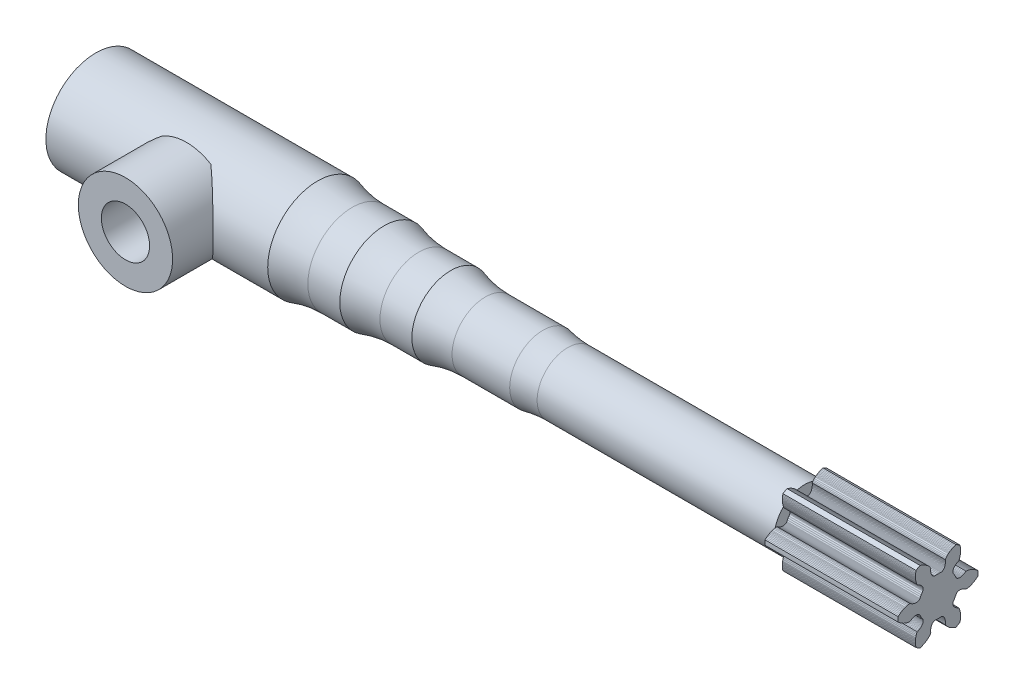
SolidWorks part; units mm, degrees
note: The reader was unsure of these and kept them because the rebuilt part matched: shared geometry of "Sketch5<2>".
ref_plane "Front Plane" through (0, 0, 0) normal (1, 0, 0) x (0, 1, 0)
ref_plane "Top Plane" through (0, 0, 0) normal (0, 0, 1) x (0, 1, 0)
ref_plane "Right Plane" through (0, 0, 0) normal (0, 1, 0) x (-1, 0, 0)
sketch "Sketch1" plane through (0, 0, 0) normal (1, 0, 0) x (0, 1, 0)
  line L0 (-1.7029, 2.65) -> (1.7029, 2.65)
  line L1 (-1.6733, 2.55) -> (1.6733, 2.55) construction
  circle A0 centre (0, 0) radius 3.15 construction
  circle A1 centre (0, 0) radius 4.5
  circle A2 centre (0, 0) radius 3.05
  dimension "D1" = 0.1
  dimension "D2" = 6.1
  dimension "D4" = 9
  dimension "D5" = 0.2
extrude "Boss-Extrude1" add sketch "Sketch1" along normal blind 14
sketch "Sketch2" plane through (14, 0, 0) normal (1, 0, 0) x (0, 1, 0)
  circle A0 centre (0, 0) radius 4.5
  circle A1 centre (0, 0) radius 4.5 construction
extrude "Boss-Extrude2" add sketch "Sketch2" along normal blind 6
sketch "Sketch5" plane through (0, 0, 2.65) normal (0, 0, -1) x (1, 0, 0)
  line L0 (0, 0) -> (14, 0) construction
  line L4 (0, 1.51) -> (0, -1.51)
  line L5 (0, -1.51) -> (14, -1.51)
  line L6 (14, -1.51) -> (14, 1.51)
  line L7 (14, 1.51) -> (0, 1.51)
  line L8 (0, 1.51) -> (0, -1.51) construction
  line L9 (0, -1.51) -> (14, -1.51) construction
  line L10 (14, -1.51) -> (14, 1.51) construction
  line L11 (14, 1.51) -> (0, 1.51) construction
  circle A0 centre (10.825, 0) radius 2.175
  circle A1 centre (10.825, 0) radius 4.25
  dimension "D3" = 4.35
  dimension "D4" = 8.5
  dimension "D2" = 1
  dimension "D1" = 0
extrude "Boss-Extrude4" add sketch "Sketch5" against normal blind 5.5
extrude "Cut-Extrude2" cut sketch "Sketch5<2>" against normal through all contours A0
sketch "Sketch5<2>" plane through (0, 0, 2.65) normal (0, 0, -1) x (1, 0, 0) same geometry as "Sketch5"
sketch "Sketch3" plane through (20, 0, 0) normal (1, 0, 0) x (0, 1, 0)
  circle A70 centre (0, 0) radius 4.5 construction
  circle A71 centre (0, 0) radius 4.5
  circle A72 centre (0, 0) radius 4
  dimension "D1" = 0.5
extrude "Boss-Extrude5" add sketch "Sketch3" along normal blind 6 contours A72
sketch "Sketch6" plane through (26, 0, 0) normal (1, 0, 0) x (0, 1, 0)
  circle A0 centre (0, 0) radius 4 construction
  circle A1 centre (0, 0) radius 4
  circle A2 centre (0, 0) radius 3.5
  dimension "D1" = 0.5
extrude "Boss-Extrude6" add sketch "Sketch6" along normal blind 6 contours A2
sketch "Sketch7" plane through (32, 0, 0) normal (1, 0, 0) x (0, 1, 0)
  circle A0 centre (0, 0) radius 3.5 construction
  circle A1 centre (0, 0) radius 3.5
  circle A2 centre (0, 0) radius 3
  dimension "D1" = 0.5
extrude "Boss-Extrude7" add sketch "Sketch7" along normal blind 8.32 contours A2
sketch "Sketch8" plane through (40.32, 0, 0) normal (1, 0, 0) x (0, 1, 0)
  circle A0 centre (0, 0) radius 3 construction
  circle A1 centre (0, 0) radius 3
  circle A2 centre (0, 0) radius 2.75
  dimension "D1" = 0.25
extrude "Boss-Extrude8" add sketch "Sketch8" along normal blind 23.6 contours A2
sketch "Sketch10" plane through (63.92, 0, 0) normal (1, 0, 0) x (0, 1, 0)
  line L0 (-0.2676, -3.5489) -> (-0.3294, -3.471)
  line L1 (-0.3294, -3.471) -> (-0.3862, -3.3929)
  line L2 (-0.3862, -3.3929) -> (-0.437, -3.3167)
  line L3 (-0.437, -3.3167) -> (-0.483, -3.2409)
  line L4 (-0.483, -3.2409) -> (-0.5222, -3.1698)
  line L5 (-0.5222, -3.1698) -> (-0.5578, -3.0984)
  line L6 (-0.5578, -3.0984) -> (-0.5877, -3.0315)
  line L7 (-0.5877, -3.0315) -> (-0.6137, -2.9659)
  line L8 (-0.6137, -2.9659) -> (-0.6533, -2.8448)
  line L9 (-0.6533, -2.8448) -> (-0.6779, -2.7405)
  line L10 (-0.6779, -2.7405) -> (-0.6912, -2.651)
  line L11 (-0.6912, -2.651) -> (-0.6959, -2.5788)
  line L12 (-0.6959, -2.5788) -> (-0.6958, -2.5445)
  line L13 (-0.6958, -2.5445) -> (-0.6453, -2.4741)
  line L14 (-0.6453, -2.4741) -> (-0.6007, -2.4024)
  line L15 (-0.6007, -2.4024) -> (-0.5632, -2.3314)
  line L16 (-0.5632, -2.3314) -> (-0.5325, -2.2616)
  line L17 (-0.5325, -2.2616) -> (-0.5087, -2.1934)
  line L18 (-0.5087, -2.1934) -> (-0.4913, -2.1274)
  line L19 (-0.4913, -2.1274) -> (-0.4802, -2.0638)
  line L20 (-0.4802, -2.0638) -> (-0.4753, -2.0031)
  line L21 (-0.4753, -2.0031) -> (-0.4761, -1.9458)
  line L22 (-0.4761, -1.9458) -> (-0.4824, -1.8921)
  line L23 (-0.4824, -1.8921) -> (-0.4939, -1.8425)
  line L24 (-0.4939, -1.8425) -> (-0.5102, -1.7972)
  line L25 (-0.5102, -1.7972) -> (-0.5311, -1.7566)
  line L26 (-0.5311, -1.7566) -> (-0.5561, -1.721)
  line L27 (-0.5561, -1.721) -> (-0.5848, -1.6906)
  line L28 (-0.5848, -1.6906) -> (-0.6169, -1.6657)
  line L29 (-0.6169, -1.6657) -> (-0.6341, -1.6554)
  line L30 (-0.6341, -1.6554) -> (-0.7518, -1.6022)
  line L31 (-0.7518, -1.6022) -> (-0.8694, -1.5401)
  line L32 (-0.8694, -1.5401) -> (-0.9819, -1.4693)
  line L33 (-0.9819, -1.4693) -> (-1.0868, -1.394)
  line L34 (-1.0868, -1.394) -> (-1.1043, -1.3843)
  line L35 (-1.1043, -1.3843) -> (-1.142, -1.3689)
  line L36 (-1.142, -1.3689) -> (-1.1827, -1.3592)
  line L37 (-1.1827, -1.3592) -> (-1.226, -1.3554)
  line L38 (-1.226, -1.3554) -> (-1.2716, -1.3576)
  line L39 (-1.2716, -1.3576) -> (-1.319, -1.3661)
  line L40 (-1.319, -1.3661) -> (-1.3677, -1.381)
  line L41 (-1.3677, -1.381) -> (-1.4174, -1.4023)
  line L42 (-1.4174, -1.4023) -> (-1.4674, -1.4303)
  line L43 (-1.4674, -1.4303) -> (-1.5175, -1.465)
  line L44 (-1.5175, -1.465) -> (-1.567, -1.5063)
  line L45 (-1.567, -1.5063) -> (-1.6155, -1.5544)
  line L46 (-1.6155, -1.5544) -> (-1.6626, -1.6091)
  line L47 (-1.6626, -1.6091) -> (-1.7077, -1.6706)
  line L48 (-1.7077, -1.6706) -> (-1.7504, -1.7386)
  line L49 (-1.7504, -1.7386) -> (-1.7903, -1.813)
  line L50 (-1.7903, -1.813) -> (-1.826, -1.892)
  line L51 (-1.826, -1.892) -> (-1.8556, -1.9092)
  line L52 (-1.8556, -1.9092) -> (-1.9205, -1.9413)
  line L53 (-1.9205, -1.9413) -> (-2.0047, -1.9745)
  line L54 (-2.0047, -1.9745) -> (-2.1073, -2.0053)
  line L55 (-2.1073, -2.0053) -> (-2.2319, -2.0316)
  line L56 (-2.2319, -2.0316) -> (-2.3018, -2.0418)
  line L57 (-2.3018, -2.0418) -> (-2.3747, -2.0494)
  line L58 (-2.3747, -2.0494) -> (-2.4543, -2.0543)
  line L59 (-2.4543, -2.0543) -> (-2.5355, -2.0559)
  line L60 (-2.5355, -2.0559) -> (-2.6241, -2.054)
  line L61 (-2.6241, -2.054) -> (-2.7155, -2.0481)
  line L62 (-2.7155, -2.0481) -> (-2.8116, -2.0379)
  line L63 (-2.8116, -2.0379) -> (-2.9099, -2.0233)
  line L64 (-2.9099, -2.0233) -> (-3.0047, -2.0052)
  line L65 (-3.2164, -1.6385) -> (-3.1847, -1.5473)
  line L66 (-3.1847, -1.5473) -> (-3.1482, -1.4549)
  line L67 (-3.1482, -1.4549) -> (-3.109, -1.3666)
  line L68 (-3.109, -1.3666) -> (-3.0684, -1.2845)
  line L69 (-3.0684, -1.2845) -> (-3.0257, -1.2068)
  line L70 (-3.0257, -1.2068) -> (-2.9837, -1.1373)
  line L71 (-2.9837, -1.1373) -> (-2.9397, -1.0708)
  line L72 (-2.9397, -1.0708) -> (-2.8967, -1.0114)
  line L73 (-2.8967, -1.0114) -> (-2.8529, -0.9561)
  line L74 (-2.8529, -0.9561) -> (-2.7678, -0.8613)
  line L75 (-2.7678, -0.8613) -> (-2.6898, -0.7879)
  line L76 (-2.6898, -0.7879) -> (-2.619, -0.7315)
  line L77 (-2.619, -0.7315) -> (-2.5587, -0.6914)
  line L78 (-2.5587, -0.6914) -> (-2.529, -0.6743)
  line L79 (-2.529, -0.6743) -> (-2.4428, -0.6829)
  line L80 (-2.4428, -0.6829) -> (-2.3584, -0.6856)
  line L81 (-2.3584, -0.6856) -> (-2.2781, -0.6826)
  line L82 (-2.2781, -0.6826) -> (-2.2024, -0.6742)
  line L83 (-2.2024, -0.6742) -> (-2.1314, -0.6608)
  line L84 (-2.1314, -0.6608) -> (-2.0655, -0.6428)
  line L85 (-2.0655, -0.6428) -> (-2.0049, -0.6206)
  line L86 (-2.0049, -0.6206) -> (-1.9499, -0.5946)
  line L87 (-1.9499, -0.5946) -> (-1.9006, -0.5653)
  line L88 (-1.9006, -0.5653) -> (-1.8573, -0.533)
  line L89 (-1.8573, -0.533) -> (-1.8201, -0.4982)
  line L90 (-1.8201, -0.4982) -> (-1.789, -0.4614)
  line L91 (-1.789, -0.4614) -> (-1.7643, -0.423)
  line L92 (-1.7643, -0.423) -> (-1.746, -0.3836)
  line L93 (-1.746, -0.3836) -> (-1.734, -0.3435)
  line L94 (-1.734, -0.3435) -> (-1.7285, -0.3032)
  line L95 (-1.7285, -0.3032) -> (-1.7282, -0.2831)
  line L96 (-1.7282, -0.2831) -> (-1.7409, -0.1546)
  line L97 (-1.7409, -0.1546) -> (-1.746, -0.0218)
  line L98 (-1.746, -0.0218) -> (-1.7409, 0.111)
  line L99 (-1.7409, 0.111) -> (-1.7282, 0.2395)
  line L100 (-1.7282, 0.2395) -> (-1.7285, 0.2596)
  line L101 (-1.7285, 0.2596) -> (-1.734, 0.2999)
  line L102 (-1.734, 0.2999) -> (-1.746, 0.34)
  line L103 (-1.746, 0.34) -> (-1.7643, 0.3794)
  line L104 (-1.7643, 0.3794) -> (-1.789, 0.4178)
  line L105 (-1.789, 0.4178) -> (-1.8201, 0.4546)
  line L106 (-1.8201, 0.4546) -> (-1.8573, 0.4894)
  line L107 (-1.8573, 0.4894) -> (-1.9006, 0.5217)
  line L108 (-1.9006, 0.5217) -> (-1.9499, 0.551)
  line L109 (-1.9499, 0.551) -> (-2.0049, 0.577)
  line L110 (-2.0049, 0.577) -> (-2.0655, 0.5992)
  line L111 (-2.0655, 0.5992) -> (-2.1314, 0.6172)
  line L112 (-2.1314, 0.6172) -> (-2.2024, 0.6306)
  line L113 (-2.2024, 0.6306) -> (-2.2781, 0.639)
  line L114 (-2.2781, 0.639) -> (-2.3584, 0.642)
  line L115 (-2.3584, 0.642) -> (-2.4428, 0.6393)
  line L116 (-2.4428, 0.6393) -> (-2.529, 0.6307)
  line L117 (-2.529, 0.6307) -> (-2.5587, 0.6478)
  line L118 (-2.5587, 0.6478) -> (-2.619, 0.6879)
  line L119 (-2.619, 0.6879) -> (-2.6898, 0.7443)
  line L120 (-2.6898, 0.7443) -> (-2.7678, 0.8177)
  line L121 (-2.7678, 0.8177) -> (-2.8529, 0.9125)
  line L122 (-2.8529, 0.9125) -> (-2.8967, 0.9678)
  line L123 (-2.8967, 0.9678) -> (-2.9397, 1.0272)
  line L124 (-2.9397, 1.0272) -> (-2.9837, 1.0937)
  line L125 (-2.9837, 1.0937) -> (-3.0257, 1.1632)
  line L126 (-3.0257, 1.1632) -> (-3.0684, 1.2409)
  line L127 (-3.0684, 1.2409) -> (-3.109, 1.323)
  line L128 (-3.109, 1.323) -> (-3.1482, 1.4113)
  line L129 (-3.1482, 1.4113) -> (-3.1847, 1.5037)
  line L130 (-3.1847, 1.5037) -> (-3.2164, 1.5949)
  line L131 (-3.0047, 1.9616) -> (-2.9099, 1.9797)
  line L132 (-2.9099, 1.9797) -> (-2.8116, 1.9943)
  line L133 (-2.8116, 1.9943) -> (-2.7155, 2.0045)
  line L134 (-2.7155, 2.0045) -> (-2.6241, 2.0104)
  line L135 (-2.6241, 2.0104) -> (-2.5355, 2.0123)
  line L136 (-2.5355, 2.0123) -> (-2.4543, 2.0107)
  line L137 (-2.4543, 2.0107) -> (-2.3747, 2.0058)
  line L138 (-2.3747, 2.0058) -> (-2.3018, 1.9983)
  line L139 (-2.3018, 1.9983) -> (-2.2319, 1.988)
  line L140 (-2.2319, 1.988) -> (-2.1073, 1.9617)
  line L141 (-2.1073, 1.9617) -> (-2.0047, 1.9309)
  line L142 (-2.0047, 1.9309) -> (-1.9205, 1.8977)
  line L143 (-1.9205, 1.8977) -> (-1.8556, 1.8656)
  line L144 (-1.8556, 1.8656) -> (-1.826, 1.8484)
  line L145 (-1.826, 1.8484) -> (-1.7903, 1.7694)
  line L146 (-1.7903, 1.7694) -> (-1.7504, 1.695)
  line L147 (-1.7504, 1.695) -> (-1.7077, 1.627)
  line L148 (-1.7077, 1.627) -> (-1.6626, 1.5656)
  line L149 (-1.6626, 1.5656) -> (-1.6155, 1.5108)
  line L150 (-1.6155, 1.5108) -> (-1.567, 1.4627)
  line L151 (-1.567, 1.4627) -> (-1.5175, 1.4214)
  line L152 (-1.5175, 1.4214) -> (-1.4674, 1.3867)
  line L153 (-1.4674, 1.3867) -> (-1.4174, 1.3587)
  line L154 (-1.4174, 1.3587) -> (-1.3677, 1.3374)
  line L155 (-1.3677, 1.3374) -> (-1.319, 1.3225)
  line L156 (-1.319, 1.3225) -> (-1.2716, 1.314)
  line L157 (-1.2716, 1.314) -> (-1.226, 1.3118)
  line L158 (-1.226, 1.3118) -> (-1.1827, 1.3156)
  line L159 (-1.1827, 1.3156) -> (-1.142, 1.3254)
  line L160 (-1.142, 1.3254) -> (-1.1043, 1.3407)
  line L161 (-1.1043, 1.3407) -> (-1.0868, 1.3504)
  line L162 (-1.0868, 1.3504) -> (-0.9819, 1.4257)
  line L163 (-0.9819, 1.4257) -> (-0.8694, 1.4965)
  line L164 (-0.8694, 1.4965) -> (-0.7518, 1.5586)
  line L165 (-0.7518, 1.5586) -> (-0.6341, 1.6118)
  line L166 (-0.6341, 1.6118) -> (-0.6169, 1.6221)
  line L167 (-0.6169, 1.6221) -> (-0.5848, 1.647)
  line L168 (-0.5848, 1.647) -> (-0.5561, 1.6774)
  line L169 (-0.5561, 1.6774) -> (-0.5311, 1.713)
  line L170 (-0.5311, 1.713) -> (-0.5102, 1.7536)
  line L171 (-0.5102, 1.7536) -> (-0.4939, 1.7989)
  line L172 (-0.4939, 1.7989) -> (-0.4824, 1.8485)
  line L173 (-0.4824, 1.8485) -> (-0.4761, 1.9022)
  line L174 (-0.4761, 1.9022) -> (-0.4753, 1.9596)
  line L175 (-0.4753, 1.9596) -> (-0.4802, 2.0202)
  line L176 (-0.4802, 2.0202) -> (-0.4913, 2.0838)
  line L177 (-0.4913, 2.0838) -> (-0.5087, 2.1498)
  line L178 (-0.5087, 2.1498) -> (-0.5325, 2.218)
  line L179 (-0.5325, 2.218) -> (-0.5632, 2.2878)
  line L180 (-0.5632, 2.2878) -> (-0.6007, 2.3588)
  line L181 (-0.6007, 2.3588) -> (-0.6453, 2.4305)
  line L182 (-0.6453, 2.4305) -> (-0.6958, 2.5009)
  line L183 (-0.6958, 2.5009) -> (-0.6959, 2.5352)
  line L184 (-0.6959, 2.5352) -> (-0.6912, 2.6074)
  line L185 (-0.6912, 2.6074) -> (-0.6779, 2.6969)
  line L186 (-0.6779, 2.6969) -> (-0.6533, 2.8012)
  line L187 (-0.6533, 2.8012) -> (-0.6137, 2.9223)
  line L188 (-0.6137, 2.9223) -> (-0.5877, 2.9879)
  line L189 (-0.5877, 2.9879) -> (-0.5578, 3.0548)
  line L190 (-0.5578, 3.0548) -> (-0.5222, 3.1262)
  line L191 (-0.5222, 3.1262) -> (-0.483, 3.1973)
  line L192 (-0.483, 3.1973) -> (-0.437, 3.2731)
  line L193 (-0.437, 3.2731) -> (-0.3862, 3.3493)
  line L194 (-0.3862, 3.3493) -> (-0.3294, 3.4275)
  line L195 (-0.3294, 3.4275) -> (-0.2676, 3.5053)
  line L196 (-0.2676, 3.5053) -> (-0.2045, 3.5783)
  line L197 (0.2189, 3.5783) -> (0.282, 3.5053)
  line L198 (0.282, 3.5053) -> (0.3438, 3.4275)
  line L199 (0.3438, 3.4275) -> (0.4007, 3.3493)
  line L200 (0.4007, 3.3493) -> (0.4515, 3.2731)
  line L201 (0.4515, 3.2731) -> (0.4975, 3.1973)
  line L202 (0.4975, 3.1973) -> (0.5367, 3.1262)
  line L203 (0.5367, 3.1262) -> (0.5722, 3.0548)
  line L204 (0.5722, 3.0548) -> (0.6021, 2.9879)
  line L205 (0.6021, 2.9879) -> (0.6282, 2.9223)
  line L206 (0.6282, 2.9223) -> (0.6677, 2.8012)
  line L207 (0.6677, 2.8012) -> (0.6923, 2.6969)
  line L208 (0.6923, 2.6969) -> (0.7057, 2.6074)
  line L209 (0.7057, 2.6074) -> (0.7104, 2.5352)
  line L210 (0.7104, 2.5352) -> (0.7103, 2.5009)
  line L211 (0.7103, 2.5009) -> (0.6597, 2.4305)
  line L212 (0.6597, 2.4305) -> (0.6152, 2.3588)
  line L213 (0.6152, 2.3588) -> (0.5776, 2.2878)
  line L214 (0.5776, 2.2878) -> (0.547, 2.218)
  line L215 (0.547, 2.218) -> (0.5231, 2.1498)
  line L216 (0.5231, 2.1498) -> (0.5058, 2.0838)
  line L217 (0.5058, 2.0838) -> (0.4947, 2.0202)
  line L218 (0.4947, 2.0202) -> (0.4897, 1.9596)
  line L219 (0.4897, 1.9596) -> (0.4905, 1.9022)
  line L220 (0.4905, 1.9022) -> (0.4968, 1.8485)
  line L221 (0.4968, 1.8485) -> (0.5083, 1.7989)
  line L222 (0.5083, 1.7989) -> (0.5247, 1.7536)
  line L223 (0.5247, 1.7536) -> (0.5455, 1.713)
  line L224 (0.5455, 1.713) -> (0.5705, 1.6774)
  line L225 (0.5705, 1.6774) -> (0.5993, 1.647)
  line L226 (0.5993, 1.647) -> (0.6314, 1.6221)
  line L227 (0.6314, 1.6221) -> (0.6486, 1.6118)
  line L228 (0.6486, 1.6118) -> (0.7663, 1.5586)
  line L229 (0.7663, 1.5586) -> (0.8838, 1.4965)
  line L230 (0.8838, 1.4965) -> (0.9964, 1.4257)
  line L231 (0.9964, 1.4257) -> (1.1013, 1.3504)
  line L232 (1.1013, 1.3504) -> (1.1188, 1.3407)
  line L233 (1.1188, 1.3407) -> (1.1564, 1.3254)
  line L234 (1.1564, 1.3254) -> (1.1971, 1.3156)
  line L235 (1.1971, 1.3156) -> (1.2405, 1.3118)
  line L236 (1.2405, 1.3118) -> (1.2861, 1.314)
  line L237 (1.2861, 1.314) -> (1.3335, 1.3225)
  line L238 (1.3335, 1.3225) -> (1.3822, 1.3374)
  line L239 (1.3822, 1.3374) -> (1.4318, 1.3587)
  line L240 (1.4318, 1.3587) -> (1.4819, 1.3867)
  line L241 (1.4819, 1.3867) -> (1.5319, 1.4214)
  line L242 (1.5319, 1.4214) -> (1.5814, 1.4627)
  line L243 (1.5814, 1.4627) -> (1.63, 1.5108)
  line L244 (1.63, 1.5108) -> (1.6771, 1.5656)
  line L245 (1.6771, 1.5656) -> (1.7222, 1.627)
  line L246 (1.7222, 1.627) -> (1.7649, 1.695)
  line L247 (1.7649, 1.695) -> (1.8048, 1.7694)
  line L248 (1.8048, 1.7694) -> (1.8405, 1.8484)
  line L249 (1.8405, 1.8484) -> (1.8701, 1.8656)
  line L250 (1.8701, 1.8656) -> (1.935, 1.8977)
  line L251 (1.935, 1.8977) -> (2.0192, 1.9309)
  line L252 (2.0192, 1.9309) -> (2.1217, 1.9617)
  line L253 (2.1217, 1.9617) -> (2.2464, 1.988)
  line L254 (2.2464, 1.988) -> (2.3162, 1.9983)
  line L255 (2.3162, 1.9983) -> (2.3891, 2.0058)
  line L256 (2.3891, 2.0058) -> (2.4688, 2.0107)
  line L257 (2.4688, 2.0107) -> (2.55, 2.0123)
  line L258 (2.55, 2.0123) -> (2.6386, 2.0104)
  line L259 (2.6386, 2.0104) -> (2.73, 2.0045)
  line L260 (2.73, 2.0045) -> (2.8261, 1.9943)
  line L261 (2.8261, 1.9943) -> (2.9243, 1.9797)
  line L262 (2.9243, 1.9797) -> (3.0192, 1.9616)
  line L263 (3.2309, 1.5949) -> (3.1992, 1.5037)
  line L264 (3.1992, 1.5037) -> (3.1627, 1.4113)
  line L265 (3.1627, 1.4113) -> (3.1235, 1.323)
  line L266 (3.1235, 1.323) -> (3.0828, 1.2409)
  line L267 (3.0828, 1.2409) -> (3.0402, 1.1632)
  line L268 (3.0402, 1.1632) -> (2.9982, 1.0937)
  line L269 (2.9982, 1.0937) -> (2.9542, 1.0272)
  line L270 (2.9542, 1.0272) -> (2.9112, 0.9678)
  line L271 (2.9112, 0.9678) -> (2.8674, 0.9125)
  line L272 (2.8674, 0.9125) -> (2.7823, 0.8177)
  line L273 (2.7823, 0.8177) -> (2.7043, 0.7443)
  line L274 (2.7043, 0.7443) -> (2.6335, 0.6879)
  line L275 (2.6335, 0.6879) -> (2.5732, 0.6478)
  line L276 (2.5732, 0.6478) -> (2.5435, 0.6307)
  line L277 (2.5435, 0.6307) -> (2.4573, 0.6393)
  line L278 (2.4573, 0.6393) -> (2.3728, 0.642)
  line L279 (2.3728, 0.642) -> (2.2926, 0.639)
  line L280 (2.2926, 0.639) -> (2.2168, 0.6306)
  line L281 (2.2168, 0.6306) -> (2.1459, 0.6172)
  line L282 (2.1459, 0.6172) -> (2.08, 0.5992)
  line L283 (2.08, 0.5992) -> (2.0194, 0.577)
  line L284 (2.0194, 0.577) -> (1.9644, 0.551)
  line L285 (1.9644, 0.551) -> (1.9151, 0.5217)
  line L286 (1.9151, 0.5217) -> (1.8718, 0.4894)
  line L287 (1.8718, 0.4894) -> (1.8346, 0.4546)
  line L288 (1.8346, 0.4546) -> (1.8035, 0.4178)
  line L289 (1.8035, 0.4178) -> (1.7788, 0.3794)
  line L290 (1.7788, 0.3794) -> (1.7604, 0.34)
  line L291 (1.7604, 0.34) -> (1.7485, 0.2999)
  line L292 (1.7485, 0.2999) -> (1.743, 0.2596)
  line L293 (1.743, 0.2596) -> (1.7426, 0.2395)
  line L294 (1.7426, 0.2395) -> (1.7554, 0.111)
  line L295 (1.7554, 0.111) -> (1.7604, -0.0218)
  line L296 (1.7604, -0.0218) -> (1.7554, -0.1546)
  line L297 (1.7554, -0.1546) -> (1.7426, -0.2831)
  line L298 (1.7426, -0.2831) -> (1.743, -0.3032)
  line L299 (1.743, -0.3032) -> (1.7485, -0.3435)
  line L300 (1.7485, -0.3435) -> (1.7604, -0.3836)
  line L301 (1.7604, -0.3836) -> (1.7788, -0.423)
  line L302 (1.7788, -0.423) -> (1.8035, -0.4614)
  line L303 (1.8035, -0.4614) -> (1.8346, -0.4982)
  line L304 (1.8346, -0.4982) -> (1.8718, -0.533)
  line L305 (1.8718, -0.533) -> (1.9151, -0.5653)
  line L306 (1.9151, -0.5653) -> (1.9644, -0.5946)
  line L307 (1.9644, -0.5946) -> (2.0194, -0.6206)
  line L308 (2.0194, -0.6206) -> (2.08, -0.6428)
  line L309 (2.08, -0.6428) -> (2.1459, -0.6608)
  line L310 (2.1459, -0.6608) -> (2.2168, -0.6742)
  line L311 (2.2168, -0.6742) -> (2.2926, -0.6826)
  line L312 (2.2926, -0.6826) -> (2.3728, -0.6856)
  line L313 (2.3728, -0.6856) -> (2.4573, -0.6829)
  line L314 (2.4573, -0.6829) -> (2.5435, -0.6743)
  line L315 (2.5435, -0.6743) -> (2.5732, -0.6914)
  line L316 (2.5732, -0.6914) -> (2.6335, -0.7315)
  line L317 (2.6335, -0.7315) -> (2.7043, -0.7879)
  line L318 (2.7043, -0.7879) -> (2.7823, -0.8613)
  line L319 (2.7823, -0.8613) -> (2.8674, -0.9561)
  line L320 (2.8674, -0.9561) -> (2.9112, -1.0114)
  line L321 (2.9112, -1.0114) -> (2.9542, -1.0708)
  line L322 (2.9542, -1.0708) -> (2.9982, -1.1373)
  line L323 (2.9982, -1.1373) -> (3.0402, -1.2068)
  line L324 (3.0402, -1.2068) -> (3.0828, -1.2845)
  line L325 (3.0828, -1.2845) -> (3.1235, -1.3666)
  line L326 (3.1235, -1.3666) -> (3.1627, -1.4549)
  line L327 (3.1627, -1.4549) -> (3.1992, -1.5473)
  line L328 (3.1992, -1.5473) -> (3.2309, -1.6385)
  line L329 (3.0192, -2.0052) -> (2.9243, -2.0233)
  line L330 (2.9243, -2.0233) -> (2.8261, -2.0379)
  line L331 (2.8261, -2.0379) -> (2.73, -2.0481)
  line L332 (2.73, -2.0481) -> (2.6386, -2.054)
  line L333 (2.6386, -2.054) -> (2.55, -2.0559)
  line L334 (2.55, -2.0559) -> (2.4688, -2.0543)
  line L335 (2.4688, -2.0543) -> (2.3891, -2.0494)
  line L336 (2.3891, -2.0494) -> (2.3162, -2.0418)
  line L337 (2.3162, -2.0418) -> (2.2464, -2.0316)
  line L338 (2.2464, -2.0316) -> (2.1217, -2.0053)
  line L339 (2.1217, -2.0053) -> (2.0192, -1.9745)
  line L340 (2.0192, -1.9745) -> (1.935, -1.9413)
  line L341 (1.935, -1.9413) -> (1.8701, -1.9092)
  line L342 (1.8701, -1.9092) -> (1.8405, -1.892)
  line L343 (1.8405, -1.892) -> (1.8048, -1.813)
  line L344 (1.8048, -1.813) -> (1.7649, -1.7386)
  line L345 (1.7649, -1.7386) -> (1.7222, -1.6706)
  line L346 (1.7222, -1.6706) -> (1.6771, -1.6091)
  line L347 (1.6771, -1.6091) -> (1.63, -1.5544)
  line L348 (1.63, -1.5544) -> (1.5814, -1.5063)
  line L349 (1.5814, -1.5063) -> (1.5319, -1.465)
  line L350 (1.5319, -1.465) -> (1.4819, -1.4303)
  line L351 (1.4819, -1.4303) -> (1.4318, -1.4023)
  line L352 (1.4318, -1.4023) -> (1.3822, -1.381)
  line L353 (1.3822, -1.381) -> (1.3335, -1.3661)
  line L354 (1.3335, -1.3661) -> (1.2861, -1.3576)
  line L355 (1.2861, -1.3576) -> (1.2405, -1.3554)
  line L356 (1.2405, -1.3554) -> (1.1971, -1.3592)
  line L357 (1.1971, -1.3592) -> (1.1564, -1.3689)
  line L358 (1.1564, -1.3689) -> (1.1188, -1.3843)
  line L359 (1.1188, -1.3843) -> (1.1013, -1.394)
  line L360 (1.1013, -1.394) -> (0.9964, -1.4693)
  line L361 (0.9964, -1.4693) -> (0.8838, -1.5401)
  line L362 (0.8838, -1.5401) -> (0.7663, -1.6022)
  line L363 (0.7663, -1.6022) -> (0.6486, -1.6554)
  line L364 (0.6486, -1.6554) -> (0.6314, -1.6657)
  line L365 (0.6314, -1.6657) -> (0.5993, -1.6906)
  line L366 (0.5993, -1.6906) -> (0.5705, -1.721)
  line L367 (0.5705, -1.721) -> (0.5455, -1.7566)
  line L368 (0.5455, -1.7566) -> (0.5247, -1.7972)
  line L369 (0.5247, -1.7972) -> (0.5083, -1.8425)
  line L370 (0.5083, -1.8425) -> (0.4968, -1.8921)
  line L371 (0.4968, -1.8921) -> (0.4905, -1.9458)
  line L372 (0.4905, -1.9458) -> (0.4897, -2.0031)
  line L373 (0.4897, -2.0031) -> (0.4947, -2.0638)
  line L374 (0.4947, -2.0638) -> (0.5058, -2.1274)
  line L375 (0.5058, -2.1274) -> (0.5231, -2.1934)
  line L376 (0.5231, -2.1934) -> (0.547, -2.2616)
  line L377 (0.547, -2.2616) -> (0.5776, -2.3314)
  line L378 (0.5776, -2.3314) -> (0.6152, -2.4024)
  line L379 (0.6152, -2.4024) -> (0.6597, -2.4741)
  line L380 (0.6597, -2.4741) -> (0.7103, -2.5445)
  line L381 (0.7103, -2.5445) -> (0.7104, -2.5788)
  line L382 (0.7104, -2.5788) -> (0.7057, -2.651)
  line L383 (0.7057, -2.651) -> (0.6923, -2.7405)
  line L384 (0.6923, -2.7405) -> (0.6677, -2.8448)
  line L385 (0.6677, -2.8448) -> (0.6282, -2.9659)
  line L386 (0.6282, -2.9659) -> (0.6021, -3.0315)
  line L387 (0.6021, -3.0315) -> (0.5722, -3.0984)
  line L388 (0.5722, -3.0984) -> (0.5367, -3.1698)
  line L389 (0.5367, -3.1698) -> (0.4975, -3.2409)
  line L390 (0.4975, -3.2409) -> (0.4515, -3.3167)
  line L391 (0.4515, -3.3167) -> (0.4007, -3.3929)
  line L392 (0.4007, -3.3929) -> (0.3438, -3.471)
  line L393 (0.3438, -3.471) -> (0.282, -3.5489)
  line L394 (0.282, -3.5489) -> (0.2189, -3.6219)
  line L395 (-0.2045, -3.6219) -> (-0.2676, -3.5489)
  line L396 (-0.2676, -3.5489) -> (-0.3294, -3.471)
  line L397 (-0.3294, -3.471) -> (-0.3862, -3.3929)
  line L398 (-0.3862, -3.3929) -> (-0.437, -3.3167)
  line L399 (-0.437, -3.3167) -> (-0.483, -3.2409)
  line L400 (-0.483, -3.2409) -> (-0.5222, -3.1698)
  line L401 (-0.5222, -3.1698) -> (-0.5578, -3.0984)
  line L402 (-0.5578, -3.0984) -> (-0.5877, -3.0315)
  line L403 (-0.5877, -3.0315) -> (-0.6137, -2.9659)
  line L404 (-0.6137, -2.9659) -> (-0.6533, -2.8448)
  line L405 (-0.6533, -2.8448) -> (-0.6779, -2.7405)
  line L406 (-0.6779, -2.7405) -> (-0.6912, -2.651)
  line L407 (-0.6912, -2.651) -> (-0.6959, -2.5788)
  line L408 (-0.6959, -2.5788) -> (-0.6958, -2.5445)
  line L409 (-0.6958, -2.5445) -> (-0.6453, -2.4741)
  line L410 (-0.6453, -2.4741) -> (-0.6007, -2.4024)
  line L411 (-0.6007, -2.4024) -> (-0.5632, -2.3314)
  line L412 (-0.5632, -2.3314) -> (-0.5325, -2.2616)
  line L413 (-0.5325, -2.2616) -> (-0.5087, -2.1934)
  line L414 (-0.5087, -2.1934) -> (-0.4913, -2.1274)
  line L415 (-0.4913, -2.1274) -> (-0.4802, -2.0638)
  line L416 (-0.4802, -2.0638) -> (-0.4753, -2.0031)
  line L417 (-0.4753, -2.0031) -> (-0.4761, -1.9458)
  line L418 (-0.4761, -1.9458) -> (-0.4824, -1.8921)
  line L419 (-0.4824, -1.8921) -> (-0.4939, -1.8425)
  line L420 (-0.4939, -1.8425) -> (-0.5102, -1.7972)
  line L421 (-0.5102, -1.7972) -> (-0.5311, -1.7566)
  line L422 (-0.5311, -1.7566) -> (-0.5561, -1.721)
  line L423 (-0.5561, -1.721) -> (-0.5848, -1.6906)
  line L424 (-0.5848, -1.6906) -> (-0.6169, -1.6657)
  line L425 (-0.6169, -1.6657) -> (-0.6341, -1.6554)
  line L426 (-0.6341, -1.6554) -> (-0.7518, -1.6022)
  line L427 (-0.7518, -1.6022) -> (-0.8694, -1.5401)
  line L428 (-0.8694, -1.5401) -> (-0.9819, -1.4693)
  line L429 (-0.9819, -1.4693) -> (-1.0868, -1.394)
  line L430 (-1.0868, -1.394) -> (-1.1043, -1.3843)
  line L431 (-1.1043, -1.3843) -> (-1.142, -1.3689)
  line L432 (-1.142, -1.3689) -> (-1.1827, -1.3592)
  line L433 (-1.1827, -1.3592) -> (-1.226, -1.3554)
  line L434 (-1.226, -1.3554) -> (-1.2716, -1.3576)
  line L435 (-1.2716, -1.3576) -> (-1.319, -1.3661)
  line L436 (-1.319, -1.3661) -> (-1.3677, -1.381)
  line L437 (-1.3677, -1.381) -> (-1.4174, -1.4023)
  line L438 (-1.4174, -1.4023) -> (-1.4674, -1.4303)
  line L439 (-1.4674, -1.4303) -> (-1.5175, -1.465)
  line L440 (-1.5175, -1.465) -> (-1.567, -1.5063)
  line L441 (-1.567, -1.5063) -> (-1.6155, -1.5544)
  line L442 (-1.6155, -1.5544) -> (-1.6626, -1.6091)
  line L443 (-1.6626, -1.6091) -> (-1.7077, -1.6706)
  line L444 (-1.7077, -1.6706) -> (-1.7504, -1.7386)
  line L445 (-1.7504, -1.7386) -> (-1.7903, -1.813)
  line L446 (-1.7903, -1.813) -> (-1.826, -1.892)
  line L447 (-1.826, -1.892) -> (-1.8556, -1.9092)
  line L448 (-1.8556, -1.9092) -> (-1.9205, -1.9413)
  line L449 (-1.9205, -1.9413) -> (-2.0047, -1.9745)
  line L450 (-2.0047, -1.9745) -> (-2.1073, -2.0053)
  line L451 (-2.1073, -2.0053) -> (-2.2319, -2.0316)
  line L452 (-2.2319, -2.0316) -> (-2.3018, -2.0418)
  line L453 (-2.3018, -2.0418) -> (-2.3747, -2.0494)
  line L454 (-2.3747, -2.0494) -> (-2.4543, -2.0543)
  line L455 (-2.4543, -2.0543) -> (-2.5355, -2.0559)
  line L456 (-2.5355, -2.0559) -> (-2.6241, -2.054)
  line L457 (-2.6241, -2.054) -> (-2.7155, -2.0481)
  line L458 (-2.7155, -2.0481) -> (-2.8116, -2.0379)
  line L459 (-2.8116, -2.0379) -> (-2.9099, -2.0233)
  line L460 (-2.9099, -2.0233) -> (-3.0047, -2.0052)
  line L461 (-3.2164, -1.6385) -> (-3.1847, -1.5473)
  line L462 (-3.1847, -1.5473) -> (-3.1482, -1.4549)
  line L463 (-3.1482, -1.4549) -> (-3.109, -1.3666)
  line L464 (-3.109, -1.3666) -> (-3.0684, -1.2845)
  line L465 (-3.0684, -1.2845) -> (-3.0257, -1.2068)
  line L466 (-3.0257, -1.2068) -> (-2.9837, -1.1373)
  line L467 (-2.9837, -1.1373) -> (-2.9397, -1.0708)
  line L468 (-2.9397, -1.0708) -> (-2.8967, -1.0114)
  line L469 (-2.8967, -1.0114) -> (-2.8529, -0.9561)
  line L470 (-2.8529, -0.9561) -> (-2.7678, -0.8613)
  line L471 (-2.7678, -0.8613) -> (-2.6898, -0.7879)
  line L472 (-2.6898, -0.7879) -> (-2.619, -0.7315)
  line L473 (-2.619, -0.7315) -> (-2.5587, -0.6914)
  line L474 (-2.5587, -0.6914) -> (-2.529, -0.6743)
  line L475 (-2.529, -0.6743) -> (-2.4428, -0.6829)
  line L476 (-2.4428, -0.6829) -> (-2.3584, -0.6856)
  line L477 (-2.3584, -0.6856) -> (-2.2781, -0.6826)
  line L478 (-2.2781, -0.6826) -> (-2.2024, -0.6742)
  line L479 (-2.2024, -0.6742) -> (-2.1314, -0.6608)
  line L480 (-2.1314, -0.6608) -> (-2.0655, -0.6428)
  line L481 (-2.0655, -0.6428) -> (-2.0049, -0.6206)
  line L482 (-2.0049, -0.6206) -> (-1.9499, -0.5946)
  line L483 (-1.9499, -0.5946) -> (-1.9006, -0.5653)
  line L484 (-1.9006, -0.5653) -> (-1.8573, -0.533)
  line L485 (-1.8573, -0.533) -> (-1.8201, -0.4982)
  line L486 (-1.8201, -0.4982) -> (-1.789, -0.4614)
  line L487 (-1.789, -0.4614) -> (-1.7643, -0.423)
  line L488 (-1.7643, -0.423) -> (-1.746, -0.3836)
  line L489 (-1.746, -0.3836) -> (-1.734, -0.3435)
  line L490 (-1.734, -0.3435) -> (-1.7285, -0.3032)
  line L491 (-1.7285, -0.3032) -> (-1.7282, -0.2831)
  line L492 (-1.7282, -0.2831) -> (-1.7409, -0.1546)
  line L493 (-1.7409, -0.1546) -> (-1.746, -0.0218)
  line L494 (-1.746, -0.0218) -> (-1.7409, 0.111)
  line L495 (-1.7409, 0.111) -> (-1.7282, 0.2395)
  line L496 (-1.7282, 0.2395) -> (-1.7285, 0.2596)
  line L497 (-1.7285, 0.2596) -> (-1.734, 0.2999)
  line L498 (-1.734, 0.2999) -> (-1.746, 0.34)
  line L499 (-1.746, 0.34) -> (-1.7643, 0.3794)
  line L500 (-1.7643, 0.3794) -> (-1.789, 0.4178)
  line L501 (-1.789, 0.4178) -> (-1.8201, 0.4546)
  line L502 (-1.8201, 0.4546) -> (-1.8573, 0.4894)
  line L503 (-1.8573, 0.4894) -> (-1.9006, 0.5217)
  line L504 (-1.9006, 0.5217) -> (-1.9499, 0.551)
  line L505 (-1.9499, 0.551) -> (-2.0049, 0.577)
  line L506 (-2.0049, 0.577) -> (-2.0655, 0.5992)
  line L507 (-2.0655, 0.5992) -> (-2.1314, 0.6172)
  line L508 (-2.1314, 0.6172) -> (-2.2024, 0.6306)
  line L509 (-2.2024, 0.6306) -> (-2.2781, 0.639)
  line L510 (-2.2781, 0.639) -> (-2.3584, 0.642)
  line L511 (-2.3584, 0.642) -> (-2.4428, 0.6393)
  line L512 (-2.4428, 0.6393) -> (-2.529, 0.6307)
  line L513 (-2.529, 0.6307) -> (-2.5587, 0.6478)
  line L514 (-2.5587, 0.6478) -> (-2.619, 0.6879)
  line L515 (-2.619, 0.6879) -> (-2.6898, 0.7443)
  line L516 (-2.6898, 0.7443) -> (-2.7678, 0.8177)
  line L517 (-2.7678, 0.8177) -> (-2.8529, 0.9125)
  line L518 (-2.8529, 0.9125) -> (-2.8967, 0.9678)
  line L519 (-2.8967, 0.9678) -> (-2.9397, 1.0272)
  line L520 (-2.9397, 1.0272) -> (-2.9837, 1.0937)
  line L521 (-2.9837, 1.0937) -> (-3.0257, 1.1632)
  line L522 (-3.0257, 1.1632) -> (-3.0684, 1.2409)
  line L523 (-3.0684, 1.2409) -> (-3.109, 1.323)
  line L524 (-3.109, 1.323) -> (-3.1482, 1.4113)
  line L525 (-3.1482, 1.4113) -> (-3.1847, 1.5037)
  line L526 (-3.1847, 1.5037) -> (-3.2164, 1.5949)
  line L527 (-3.0047, 1.9616) -> (-2.9099, 1.9797)
  line L528 (-2.9099, 1.9797) -> (-2.8116, 1.9943)
  line L529 (-2.8116, 1.9943) -> (-2.7155, 2.0045)
  line L530 (-2.7155, 2.0045) -> (-2.6241, 2.0104)
  line L531 (-2.6241, 2.0104) -> (-2.5355, 2.0123)
  line L532 (-2.5355, 2.0123) -> (-2.4543, 2.0107)
  line L533 (-2.4543, 2.0107) -> (-2.3747, 2.0058)
  line L534 (-2.3747, 2.0058) -> (-2.3018, 1.9983)
  line L535 (-2.3018, 1.9983) -> (-2.2319, 1.988)
  line L536 (-2.2319, 1.988) -> (-2.1073, 1.9617)
  line L537 (-2.1073, 1.9617) -> (-2.0047, 1.9309)
  line L538 (-2.0047, 1.9309) -> (-1.9205, 1.8977)
  line L539 (-1.9205, 1.8977) -> (-1.8556, 1.8656)
  line L540 (-1.8556, 1.8656) -> (-1.826, 1.8484)
  line L541 (-1.826, 1.8484) -> (-1.7903, 1.7694)
  line L542 (-1.7903, 1.7694) -> (-1.7504, 1.695)
  line L543 (-1.7504, 1.695) -> (-1.7077, 1.627)
  line L544 (-1.7077, 1.627) -> (-1.6626, 1.5656)
  line L545 (-1.6626, 1.5656) -> (-1.6155, 1.5108)
  line L546 (-1.6155, 1.5108) -> (-1.567, 1.4627)
  line L547 (-1.567, 1.4627) -> (-1.5175, 1.4214)
  line L548 (-1.5175, 1.4214) -> (-1.4674, 1.3867)
  line L549 (-1.4674, 1.3867) -> (-1.4174, 1.3587)
  line L550 (-1.4174, 1.3587) -> (-1.3677, 1.3374)
  line L551 (-1.3677, 1.3374) -> (-1.319, 1.3225)
  line L552 (-1.319, 1.3225) -> (-1.2716, 1.314)
  line L553 (-1.2716, 1.314) -> (-1.226, 1.3118)
  line L554 (-1.226, 1.3118) -> (-1.1827, 1.3156)
  line L555 (-1.1827, 1.3156) -> (-1.142, 1.3254)
  line L556 (-1.142, 1.3254) -> (-1.1043, 1.3407)
  line L557 (-1.1043, 1.3407) -> (-1.0868, 1.3504)
  line L558 (-1.0868, 1.3504) -> (-0.9819, 1.4257)
  line L559 (-0.9819, 1.4257) -> (-0.8694, 1.4965)
  line L560 (-0.8694, 1.4965) -> (-0.7518, 1.5586)
  line L561 (-0.7518, 1.5586) -> (-0.6341, 1.6118)
  line L562 (-0.6341, 1.6118) -> (-0.6169, 1.6221)
  line L563 (-0.6169, 1.6221) -> (-0.5848, 1.647)
  line L564 (-0.5848, 1.647) -> (-0.5561, 1.6774)
  line L565 (-0.5561, 1.6774) -> (-0.5311, 1.713)
  line L566 (-0.5311, 1.713) -> (-0.5102, 1.7536)
  line L567 (-0.5102, 1.7536) -> (-0.4939, 1.7989)
  line L568 (-0.4939, 1.7989) -> (-0.4824, 1.8485)
  line L569 (-0.4824, 1.8485) -> (-0.4761, 1.9022)
  line L570 (-0.4761, 1.9022) -> (-0.4753, 1.9596)
  line L571 (-0.4753, 1.9596) -> (-0.4802, 2.0202)
  line L572 (-0.4802, 2.0202) -> (-0.4913, 2.0838)
  line L573 (-0.4913, 2.0838) -> (-0.5087, 2.1498)
  line L574 (-0.5087, 2.1498) -> (-0.5325, 2.218)
  line L575 (-0.5325, 2.218) -> (-0.5632, 2.2878)
  line L576 (-0.5632, 2.2878) -> (-0.6007, 2.3588)
  line L577 (-0.6007, 2.3588) -> (-0.6453, 2.4305)
  line L578 (-0.6453, 2.4305) -> (-0.6958, 2.5009)
  line L579 (-0.6958, 2.5009) -> (-0.6959, 2.5352)
  line L580 (-0.6959, 2.5352) -> (-0.6912, 2.6074)
  line L581 (-0.6912, 2.6074) -> (-0.6779, 2.6969)
  line L582 (-0.6779, 2.6969) -> (-0.6533, 2.8012)
  line L583 (-0.6533, 2.8012) -> (-0.6137, 2.9223)
  line L584 (-0.6137, 2.9223) -> (-0.5877, 2.9879)
  line L585 (-0.5877, 2.9879) -> (-0.5578, 3.0548)
  line L586 (-0.5578, 3.0548) -> (-0.5222, 3.1262)
  line L587 (-0.5222, 3.1262) -> (-0.483, 3.1973)
  line L588 (-0.483, 3.1973) -> (-0.437, 3.2731)
  line L589 (-0.437, 3.2731) -> (-0.3862, 3.3493)
  line L590 (-0.3862, 3.3493) -> (-0.3294, 3.4275)
  line L591 (-0.3294, 3.4275) -> (-0.2676, 3.5053)
  line L592 (-0.2676, 3.5053) -> (-0.2045, 3.5783)
  line L593 (0.2189, 3.5783) -> (0.282, 3.5053)
  line L594 (0.282, 3.5053) -> (0.3438, 3.4275)
  line L595 (0.3438, 3.4275) -> (0.4007, 3.3493)
  line L596 (0.4007, 3.3493) -> (0.4515, 3.2731)
  line L597 (0.4515, 3.2731) -> (0.4975, 3.1973)
  line L598 (0.4975, 3.1973) -> (0.5367, 3.1262)
  line L599 (0.5367, 3.1262) -> (0.5722, 3.0548)
  line L600 (0.5722, 3.0548) -> (0.6021, 2.9879)
  line L601 (0.6021, 2.9879) -> (0.6282, 2.9223)
  line L602 (0.6282, 2.9223) -> (0.6677, 2.8012)
  line L603 (0.6677, 2.8012) -> (0.6923, 2.6969)
  line L604 (0.6923, 2.6969) -> (0.7057, 2.6074)
  line L605 (0.7057, 2.6074) -> (0.7104, 2.5352)
  line L606 (0.7104, 2.5352) -> (0.7103, 2.5009)
  line L607 (0.7103, 2.5009) -> (0.6597, 2.4305)
  line L608 (0.6597, 2.4305) -> (0.6152, 2.3588)
  line L609 (0.6152, 2.3588) -> (0.5776, 2.2878)
  line L610 (0.5776, 2.2878) -> (0.547, 2.218)
  line L611 (0.547, 2.218) -> (0.5231, 2.1498)
  line L612 (0.5231, 2.1498) -> (0.5058, 2.0838)
  line L613 (0.5058, 2.0838) -> (0.4947, 2.0202)
  line L614 (0.4947, 2.0202) -> (0.4897, 1.9596)
  line L615 (0.4897, 1.9596) -> (0.4905, 1.9022)
  line L616 (0.4905, 1.9022) -> (0.4968, 1.8485)
  line L617 (0.4968, 1.8485) -> (0.5083, 1.7989)
  line L618 (0.5083, 1.7989) -> (0.5247, 1.7536)
  line L619 (0.5247, 1.7536) -> (0.5455, 1.713)
  line L620 (0.5455, 1.713) -> (0.5705, 1.6774)
  line L621 (0.5705, 1.6774) -> (0.5993, 1.647)
  line L622 (0.5993, 1.647) -> (0.6314, 1.6221)
  line L623 (0.6314, 1.6221) -> (0.6486, 1.6118)
  line L624 (0.6486, 1.6118) -> (0.7663, 1.5586)
  line L625 (0.7663, 1.5586) -> (0.8838, 1.4965)
  line L626 (0.8838, 1.4965) -> (0.9964, 1.4257)
  line L627 (0.9964, 1.4257) -> (1.1013, 1.3504)
  line L628 (1.1013, 1.3504) -> (1.1188, 1.3407)
  line L629 (1.1188, 1.3407) -> (1.1564, 1.3254)
  line L630 (1.1564, 1.3254) -> (1.1971, 1.3156)
  line L631 (1.1971, 1.3156) -> (1.2405, 1.3118)
  line L632 (1.2405, 1.3118) -> (1.2861, 1.314)
  line L633 (1.2861, 1.314) -> (1.3335, 1.3225)
  line L634 (1.3335, 1.3225) -> (1.3822, 1.3374)
  line L635 (1.3822, 1.3374) -> (1.4318, 1.3587)
  line L636 (1.4318, 1.3587) -> (1.4819, 1.3867)
  line L637 (1.4819, 1.3867) -> (1.5319, 1.4214)
  line L638 (1.5319, 1.4214) -> (1.5814, 1.4627)
  line L639 (1.5814, 1.4627) -> (1.63, 1.5108)
  line L640 (1.63, 1.5108) -> (1.6771, 1.5656)
  line L641 (1.6771, 1.5656) -> (1.7222, 1.627)
  line L642 (1.7222, 1.627) -> (1.7649, 1.695)
  line L643 (1.7649, 1.695) -> (1.8048, 1.7694)
  line L644 (1.8048, 1.7694) -> (1.8405, 1.8484)
  line L645 (1.8405, 1.8484) -> (1.8701, 1.8656)
  line L646 (1.8701, 1.8656) -> (1.935, 1.8977)
  line L647 (1.935, 1.8977) -> (2.0192, 1.9309)
  line L648 (2.0192, 1.9309) -> (2.1217, 1.9617)
  line L649 (2.1217, 1.9617) -> (2.2464, 1.988)
  line L650 (2.2464, 1.988) -> (2.3162, 1.9983)
  line L651 (2.3162, 1.9983) -> (2.3891, 2.0058)
  line L652 (2.3891, 2.0058) -> (2.4688, 2.0107)
  line L653 (2.4688, 2.0107) -> (2.55, 2.0123)
  line L654 (2.55, 2.0123) -> (2.6386, 2.0104)
  line L655 (2.6386, 2.0104) -> (2.73, 2.0045)
  line L656 (2.73, 2.0045) -> (2.8261, 1.9943)
  line L657 (2.8261, 1.9943) -> (2.9243, 1.9797)
  line L658 (2.9243, 1.9797) -> (3.0192, 1.9616)
  line L659 (3.2309, 1.5949) -> (3.1992, 1.5037)
  line L660 (3.1992, 1.5037) -> (3.1627, 1.4113)
  line L661 (3.1627, 1.4113) -> (3.1235, 1.323)
  line L662 (3.1235, 1.323) -> (3.0828, 1.2409)
  line L663 (3.0828, 1.2409) -> (3.0402, 1.1632)
  line L664 (3.0402, 1.1632) -> (2.9982, 1.0937)
  line L665 (2.9982, 1.0937) -> (2.9542, 1.0272)
  line L666 (2.9542, 1.0272) -> (2.9112, 0.9678)
  line L667 (2.9112, 0.9678) -> (2.8674, 0.9125)
  line L668 (2.8674, 0.9125) -> (2.7823, 0.8177)
  line L669 (2.7823, 0.8177) -> (2.7043, 0.7443)
  line L670 (2.7043, 0.7443) -> (2.6335, 0.6879)
  line L671 (2.6335, 0.6879) -> (2.5732, 0.6478)
  line L672 (2.5732, 0.6478) -> (2.5435, 0.6307)
  line L673 (2.5435, 0.6307) -> (2.4573, 0.6393)
  line L674 (2.4573, 0.6393) -> (2.3728, 0.642)
  line L675 (2.3728, 0.642) -> (2.2926, 0.639)
  line L676 (2.2926, 0.639) -> (2.2168, 0.6306)
  line L677 (2.2168, 0.6306) -> (2.1459, 0.6172)
  line L678 (2.1459, 0.6172) -> (2.08, 0.5992)
  line L679 (2.08, 0.5992) -> (2.0194, 0.577)
  line L680 (2.0194, 0.577) -> (1.9644, 0.551)
  line L681 (1.9644, 0.551) -> (1.9151, 0.5217)
  line L682 (1.9151, 0.5217) -> (1.8718, 0.4894)
  line L683 (1.8718, 0.4894) -> (1.8346, 0.4546)
  line L684 (1.8346, 0.4546) -> (1.8035, 0.4178)
  line L685 (1.8035, 0.4178) -> (1.7788, 0.3794)
  line L686 (1.7788, 0.3794) -> (1.7604, 0.34)
  line L687 (1.7604, 0.34) -> (1.7485, 0.2999)
  line L688 (1.7485, 0.2999) -> (1.743, 0.2596)
  line L689 (1.743, 0.2596) -> (1.7426, 0.2395)
  line L690 (1.7426, 0.2395) -> (1.7554, 0.111)
  line L691 (1.7554, 0.111) -> (1.7604, -0.0218)
  line L692 (1.7604, -0.0218) -> (1.7554, -0.1546)
  line L693 (1.7554, -0.1546) -> (1.7426, -0.2831)
  line L694 (1.7426, -0.2831) -> (1.743, -0.3032)
  line L695 (1.743, -0.3032) -> (1.7485, -0.3435)
  line L696 (1.7485, -0.3435) -> (1.7604, -0.3836)
  line L697 (1.7604, -0.3836) -> (1.7788, -0.423)
  line L698 (1.7788, -0.423) -> (1.8035, -0.4614)
  line L699 (1.8035, -0.4614) -> (1.8346, -0.4982)
  line L700 (1.8346, -0.4982) -> (1.8718, -0.533)
  line L701 (1.8718, -0.533) -> (1.9151, -0.5653)
  line L702 (1.9151, -0.5653) -> (1.9644, -0.5946)
  line L703 (1.9644, -0.5946) -> (2.0194, -0.6206)
  line L704 (2.0194, -0.6206) -> (2.08, -0.6428)
  line L705 (2.08, -0.6428) -> (2.1459, -0.6608)
  line L706 (2.1459, -0.6608) -> (2.2168, -0.6742)
  line L707 (2.2168, -0.6742) -> (2.2926, -0.6826)
  line L708 (2.2926, -0.6826) -> (2.3728, -0.6856)
  line L709 (2.3728, -0.6856) -> (2.4573, -0.6829)
  line L710 (2.4573, -0.6829) -> (2.5435, -0.6743)
  line L711 (2.5435, -0.6743) -> (2.5732, -0.6914)
  line L712 (2.5732, -0.6914) -> (2.6335, -0.7315)
  line L713 (2.6335, -0.7315) -> (2.7043, -0.7879)
  line L714 (2.7043, -0.7879) -> (2.7823, -0.8613)
  line L715 (2.7823, -0.8613) -> (2.8674, -0.9561)
  line L716 (2.8674, -0.9561) -> (2.9112, -1.0114)
  line L717 (2.9112, -1.0114) -> (2.9542, -1.0708)
  line L718 (2.9542, -1.0708) -> (2.9982, -1.1373)
  line L719 (2.9982, -1.1373) -> (3.0402, -1.2068)
  line L720 (3.0402, -1.2068) -> (3.0828, -1.2845)
  line L721 (3.0828, -1.2845) -> (3.1235, -1.3666)
  line L722 (3.1235, -1.3666) -> (3.1627, -1.4549)
  line L723 (3.1627, -1.4549) -> (3.1992, -1.5473)
  line L724 (3.1992, -1.5473) -> (3.2309, -1.6385)
  line L725 (3.0192, -2.0052) -> (2.9243, -2.0233)
  line L726 (2.9243, -2.0233) -> (2.8261, -2.0379)
  line L727 (2.8261, -2.0379) -> (2.73, -2.0481)
  line L728 (2.73, -2.0481) -> (2.6386, -2.054)
  line L729 (2.6386, -2.054) -> (2.55, -2.0559)
  line L730 (2.55, -2.0559) -> (2.4688, -2.0543)
  line L731 (2.4688, -2.0543) -> (2.3891, -2.0494)
  line L732 (2.3891, -2.0494) -> (2.3162, -2.0418)
  line L733 (2.3162, -2.0418) -> (2.2464, -2.0316)
  line L734 (2.2464, -2.0316) -> (2.1217, -2.0053)
  line L735 (2.1217, -2.0053) -> (2.0192, -1.9745)
  line L736 (2.0192, -1.9745) -> (1.935, -1.9413)
  line L737 (1.935, -1.9413) -> (1.8701, -1.9092)
  line L738 (1.8701, -1.9092) -> (1.8405, -1.892)
  line L739 (1.8405, -1.892) -> (1.8048, -1.813)
  line L740 (1.8048, -1.813) -> (1.7649, -1.7386)
  line L741 (1.7649, -1.7386) -> (1.7222, -1.6706)
  line L742 (1.7222, -1.6706) -> (1.6771, -1.6091)
  line L743 (1.6771, -1.6091) -> (1.63, -1.5544)
  line L744 (1.63, -1.5544) -> (1.5814, -1.5063)
  line L745 (1.5814, -1.5063) -> (1.5319, -1.465)
  line L746 (1.5319, -1.465) -> (1.4819, -1.4303)
  line L747 (1.4819, -1.4303) -> (1.4318, -1.4023)
  line L748 (1.4318, -1.4023) -> (1.3822, -1.381)
  line L749 (1.3822, -1.381) -> (1.3335, -1.3661)
  line L750 (1.3335, -1.3661) -> (1.2861, -1.3576)
  line L751 (1.2861, -1.3576) -> (1.2405, -1.3554)
  line L752 (1.2405, -1.3554) -> (1.1971, -1.3592)
  line L753 (1.1971, -1.3592) -> (1.1564, -1.3689)
  line L754 (1.1564, -1.3689) -> (1.1188, -1.3843)
  line L755 (1.1188, -1.3843) -> (1.1013, -1.394)
  line L756 (1.1013, -1.394) -> (0.9964, -1.4693)
  line L757 (0.9964, -1.4693) -> (0.8838, -1.5401)
  line L758 (0.8838, -1.5401) -> (0.7663, -1.6022)
  line L759 (0.7663, -1.6022) -> (0.6486, -1.6554)
  line L760 (0.6486, -1.6554) -> (0.6314, -1.6657)
  line L761 (0.6314, -1.6657) -> (0.5993, -1.6906)
  line L762 (0.5993, -1.6906) -> (0.5705, -1.721)
  line L763 (0.5705, -1.721) -> (0.5455, -1.7566)
  line L764 (0.5455, -1.7566) -> (0.5247, -1.7972)
  line L765 (0.5247, -1.7972) -> (0.5083, -1.8425)
  line L766 (0.5083, -1.8425) -> (0.4968, -1.8921)
  line L767 (0.4968, -1.8921) -> (0.4905, -1.9458)
  line L768 (0.4905, -1.9458) -> (0.4897, -2.0031)
  line L769 (0.4897, -2.0031) -> (0.4947, -2.0638)
  line L770 (0.4947, -2.0638) -> (0.5058, -2.1274)
  line L771 (0.5058, -2.1274) -> (0.5231, -2.1934)
  line L772 (0.5231, -2.1934) -> (0.547, -2.2616)
  line L773 (0.547, -2.2616) -> (0.5776, -2.3314)
  line L774 (0.5776, -2.3314) -> (0.6152, -2.4024)
  line L775 (0.6152, -2.4024) -> (0.6597, -2.4741)
  line L776 (0.6597, -2.4741) -> (0.7103, -2.5445)
  line L777 (0.7103, -2.5445) -> (0.7104, -2.5788)
  line L778 (0.7104, -2.5788) -> (0.7057, -2.651)
  line L779 (0.7057, -2.651) -> (0.6923, -2.7405)
  line L780 (0.6923, -2.7405) -> (0.6677, -2.8448)
  line L781 (0.6677, -2.8448) -> (0.6282, -2.9659)
  line L782 (0.6282, -2.9659) -> (0.6021, -3.0315)
  line L783 (0.6021, -3.0315) -> (0.5722, -3.0984)
  line L784 (0.5722, -3.0984) -> (0.5367, -3.1698)
  line L785 (0.5367, -3.1698) -> (0.4975, -3.2409)
  line L786 (0.4975, -3.2409) -> (0.4515, -3.3167)
  line L787 (0.4515, -3.3167) -> (0.4007, -3.3929)
  line L788 (0.4007, -3.3929) -> (0.3438, -3.471)
  line L789 (0.3438, -3.471) -> (0.282, -3.5489)
  line L790 (0.282, -3.5489) -> (0.2189, -3.6219)
  arc A12 (-3.2164, -1.6385) -> (-3.0047, -2.0052) centre (0.0073, -0.0218) ccw
  arc A13 (-3.0047, 1.9616) -> (-3.2164, 1.5949) centre (0.0073, -0.0218) ccw
  arc A14 (0.2189, 3.5783) -> (-0.2045, 3.5783) centre (0.0072, -0.0218) ccw
  arc A15 (3.2309, 1.5949) -> (3.0192, 1.9616) centre (0.0072, -0.0218) ccw
  arc A16 (3.0192, -2.0052) -> (3.2309, -1.6385) centre (0.0072, -0.0218) ccw
  arc A17 (-0.2045, -3.6219) -> (0.2189, -3.6219) centre (0.0072, -0.0217) ccw
  arc A18 (-3.2164, -1.6385) -> (-3.0047, -2.0052) centre (0.0073, -0.0218) ccw
  arc A19 (-3.0047, 1.9616) -> (-3.2164, 1.5949) centre (0.0073, -0.0218) ccw
  arc A20 (0.2189, 3.5783) -> (-0.2045, 3.5783) centre (0.0072, -0.0218) ccw
  arc A21 (3.2309, 1.5949) -> (3.0192, 1.9616) centre (0.0072, -0.0218) ccw
  arc A22 (3.0192, -2.0052) -> (3.2309, -1.6385) centre (0.0072, -0.0218) ccw
  arc A23 (-0.2045, -3.6219) -> (0.2189, -3.6219) centre (0.0072, -0.0217) ccw
extrude "Boss-Extrude9" add sketch "Sketch10" along normal blind 12
fillet "Fillet1" radius 10 4 edges at (32, 0, -3) (40.32, 0, -2.75) (20, 0, -4) (26, 0, -3.5)
equation "\"clearance_support_plate_bottom_shoulder\"= 2"
equation "\"D1@Boss-Extrude8\"=\"clearance_support_plate_bottom_shoulder\" + \"support_plate_bottom_bushing_height\" + \"clearance_support_plate_gear_bottom\""
equation "\"support_plate_bottom_bushing_height\"= 18.6"
equation "\"clearance_support_plate_gear_bottom\"= 3"
